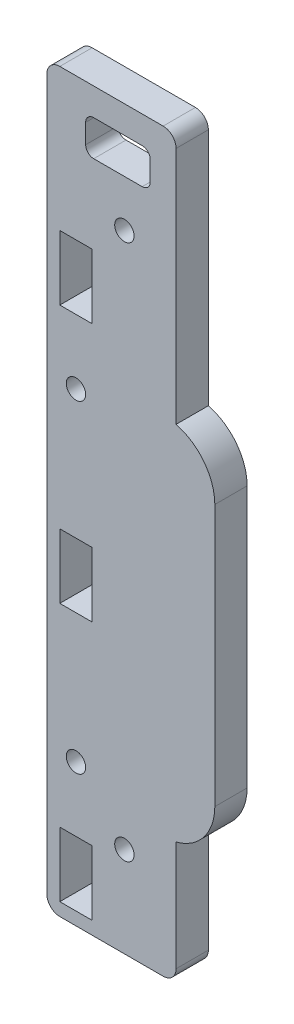
SolidWorks part; units mm, degrees
material "Maple"
ref_plane "Front Plane" through (0, 0, 0) normal (0, 0, 1) x (1, 0, 0)
ref_plane "Top Plane" through (0, 0, 0) normal (0, 1, 0) x (1, 0, 0)
ref_plane "Right Plane" through (0, 0, 0) normal (1, 0, 0) x (0, 0, -1)
sketch "Sketch1" plane through (0, 0, 0) normal (0, 0, 1) x (1, 0, 0)
  line L0 (16, 65) -> (16, 25) construction
  line L1 (0, 0) -> (24, 0)
  line L2 (0, 0) -> (0, 110)
  line L3 (0, 110) -> (24, 110)
  line L4 (24, 0) -> (24, 110)
  line L5 (16, 25) -> (16, 0) construction
  line L6 (10, 0) -> (10, 110) construction
  line L12 (16, 45) -> (24, 45) construction
  line L13 (5.25, 103.5) -> (5.25, 106.5) construction
  line L14 (4, 103.5) -> (4, 106.5)
  line L15 (6.5, 103.5) -> (6.5, 106.5)
  line L16 (12.75, 103.5) -> (12.75, 106.5) construction
  line L17 (11.5, 103.5) -> (11.5, 106.5)
  line L18 (14, 103.5) -> (14, 106.5)
  circle A0 centre (16, 65) radius 4 construction
  circle A1 centre (16, 25) radius 4 construction
  circle A6 centre (10, 12) radius 1.5
  circle A7 centre (10, 95) radius 1.5
  arc A8 (4, 103.5) -> (6.5, 103.5) centre (5.25, 103.5) ccw
  arc A9 (6.5, 106.5) -> (4, 106.5) centre (5.25, 106.5) ccw
  arc A10 (11.5, 103.5) -> (14, 103.5) centre (12.75, 103.5) ccw
  arc A11 (14, 106.5) -> (11.5, 106.5) centre (12.75, 106.5) ccw
  point P30 (5.25, 105)
  point P37 (12.75, 105)
  dimension "D2" = 8
  dimension "D10" = 6
  dimension "D16" = 3
  dimension "D3" = 40
  dimension "D4" = 16
  dimension "D5" = 110
  dimension "D6" = 9.5
  dimension "D7" = 5
  dimension "D8" = 8
  dimension "D9" = 40
  dimension "D11" = 12
  dimension "D12" = 15
  dimension "D13" = 2.5
  dimension "D14" = 3
  dimension "D15" = 5
extrude "Boss-Extrude1" add sketch "Sketch1" along normal blind 5
sketch "Sketch2" plane through (0, 0, 5) normal (0, 0, 1) x (1, 0, 0)
  line L1 (24, 110) -> (18, 110)
  line L2 (24, 110) -> (24, 73)
  line L3 (24, 73) -> (18, 73)
  line L4 (18, 110) -> (18, 73)
  line L5 (24, 0) -> (18, 0)
  line L6 (24, 0) -> (24, 17)
  line L7 (24, 17) -> (18, 17)
  line L8 (18, 0) -> (18, 17)
  dimension "D2" = 17
  dimension "D1" = 6
  dimension "D3" = 37
extrude "Cut-Extrude1" cut sketch "Sketch2" against normal through all
sketch "Sketch3" plane through (0, 0, 5) normal (0, 0, 1) x (1, 0, 0)
  line L3 (18, -2) -> (18, 0)
  line L4 (18, 110) -> (18, 112)
  line L5 (0, 0) -> (18, 0) construction
  line L6 (-2, -2) -> (18, -2)
  line L7 (-2, 112) -> (-2, -2)
  line L8 (18, 112) -> (-2, 112)
  line L9 (-2, -2) -> (18, -2)
  line L10 (-2, 112) -> (-2, -2)
  line L11 (18, 112) -> (-2, 112)
  line L12 (0, 110) -> (0, 0) construction
  line L13 (18, 110) -> (0, 110) construction
  line L14 (0, 0) -> (18, 0)
  line L15 (0, 110) -> (0, 0)
  line L16 (18, 110) -> (0, 110)
  dimension "D1" = 2
extrude "Boss-Extrude2" add sketch "Sketch3" against normal up to surface (5 mm away) up to face at (15, 50, 0)
sketch "Sketch4" plane through (0, 0, 5) normal (0, 0, 1) x (1, 0, 0)
  line L0 (2.5, 20) -> (2.5, 70) construction
  line L1 (0, 0) -> (5, 0)
  line L2 (0, 0) -> (0, 10)
  line L3 (0, 10) -> (5, 10)
  line L4 (5, 0) -> (5, 10)
  line L5 (0, 80) -> (5, 80)
  line L6 (0, 80) -> (0, 90)
  line L7 (0, 90) -> (5, 90)
  line L8 (5, 80) -> (5, 90)
  line L9 (0, 50) -> (5, 50)
  line L10 (0, 50) -> (0, 40)
  line L11 (0, 40) -> (5, 40)
  line L12 (5, 50) -> (5, 40)
  line L13 (0, 45) -> (2.5, 45) construction
  circle A0 centre (2.5, 20) radius 1.5
  circle A1 centre (2.5, 70) radius 1.5
  point P13 (0, 45)
  point P20 (2.5, 50)
  dimension "D5" = 3
  dimension "D1" = 90
  dimension "D2" = 45
  dimension "D3" = 5
  dimension "D4" = 10
  dimension "D6" = 50
extrude "Cut-Extrude2" cut sketch "Sketch4" against normal through all
fillet "Fillet1" radius 2 4 edges at (18, -2, 2.5) (-2, -2, 2.5) (-2, 112, 2.5) (18, 112, 2.5)
fillet "Fillet2" radius 8 2 edges at (24, 17, 2.5) (24, 73, 2.5)
sketch "Sketch5" plane through (0, 0, 5) normal (0, 0, 1) x (1, 0, 0)
  line L1 (5.25, 107.75) -> (12.75, 107.75)
  line L2 (5.25, 107.75) -> (5.25, 102.25)
  line L3 (5.25, 102.25) -> (12.75, 102.25)
  line L4 (12.75, 107.75) -> (12.75, 102.25)
  arc A0 (6.5, 106.5) -> (4, 106.5) centre (5.25, 106.5) ccw construction
  arc A1 (11.5, 103.5) -> (14, 103.5) centre (12.75, 103.5) ccw construction
extrude "Cut-Extrude3" cut sketch "Sketch5" against normal through all
